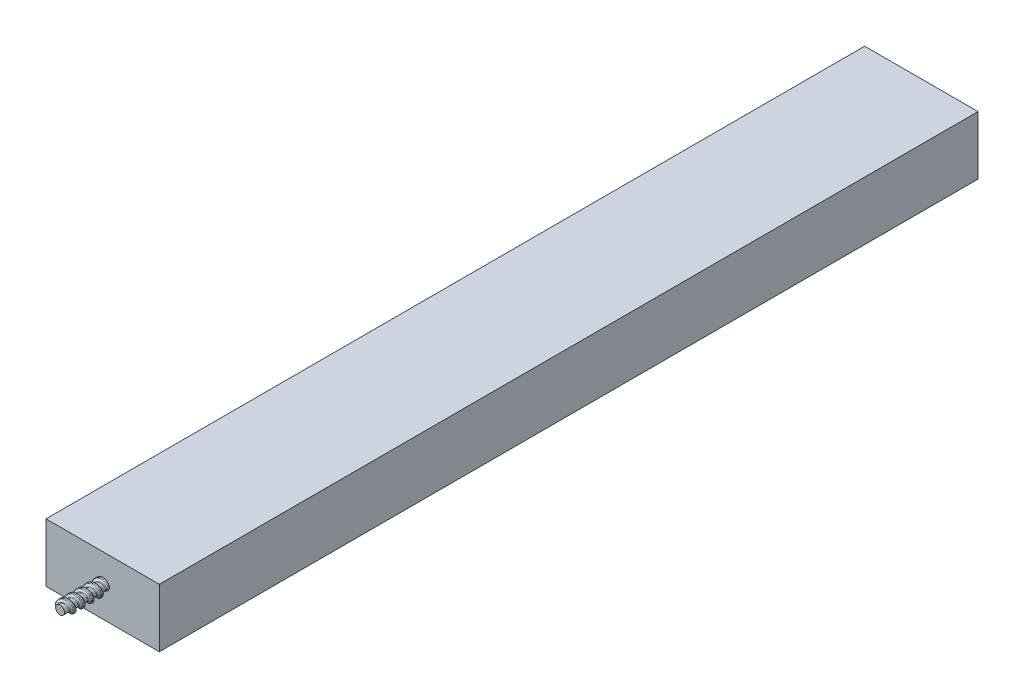
SolidWorks part; units mm, degrees
ref_plane "Front Plane" through (0, 0, 0) normal (0, 0, 1) x (1, 0, 0)
ref_plane "Top Plane" through (0, 0, 0) normal (0, 1, 0) x (1, 0, 0)
ref_plane "Right Plane" through (0, 0, 0) normal (1, 0, 0) x (0, 0, -1)
sketch "Sketch1" plane through (0, 0, 0) normal (0, 0, 1) x (1, 0, 0)
  line L1 (0, 0) -> (63.5, 0)
  line L2 (0, 0) -> (0, 32.766)
  line L3 (0, 32.766) -> (63.5, 32.766)
  line L4 (63.5, 0) -> (63.5, 32.766)
  dimension "D1" = 63.5
  dimension "D2" = 32.766
extrude "Boss-Extrude1" add sketch "Sketch1" against normal blind 482.6
sketch "Sketch2" plane through (0, 0, 0) normal (0, 0, 1) x (1, 0, 0)
  line L0 (63.5, 32.766) -> (0, 32.766) construction
  line L1 (63.5, 0) -> (63.5, 32.766) construction
  line L3 (0, 32.766) -> (63.5, 32.766)
  line L4 (0, 32.766) -> (0, 0)
  line L5 (0, 0) -> (63.5, 0)
  line L6 (63.5, 32.766) -> (63.5, 0)
  circle A0 centre (31.75, 16.383) radius 2.4574
  dimension "D1" = 4.9149
  dimension "D2" = 16.383
  dimension "D3" = 31.75
extrude "Cut-Extrude2" cut sketch "Sketch2" against normal blind 23.876
thread "Thread2" pitch 5.08 method extrude profile "Thread Profile2" start angle 0, offset 0, length 0, pitch 5.08, diameter 4.9149
ref_plane "Plane2" through (29.2926, 16.383, 0) normal (0, -1, 0) x (-1, 0, 0)
sketch "Thread Profile2" plane through (29.2926, 16.383, 0) normal (0, -1, 0) x (-1, 0, 0)
  line L0 (0, 0) -> (0, 5.08) construction
  line L1 (0, 0) -> (0, 3.6346)
  line L2 (0.508, 3.6346) -> (1.524, 3.6346) construction
  line L3 (1.524, 2.1681) -> (1.524, 1.4665)
  line L4 (1.27, 2.6081) -> (0.254, 3.1946)
  line L5 (1.27, 1.0265) -> (0.254, 0.4399)
  line L6 (0.508, 0) -> (1.524, 0) construction
  arc A0 (0.254, 3.1946) -> (0, 3.6346) centre (0.508, 3.6346) cw
  arc A1 (0.254, 0.4399) -> (0, 0) centre (0.508, 0) ccw
  arc A2 (1.524, 1.4665) -> (1.27, 1.0265) centre (1.016, 1.4665) cw
  arc A3 (1.524, 2.1681) -> (1.27, 2.6081) centre (1.016, 2.1681) ccw
  point P10 (1.524, 2.4614)
  point P17 (1.524, 1.1732)
  point P18 (0, 3.3413)
  point P19 (0, 0.2933)
  point P20 (0, 0)
  dimension "RootFillet1" = 0.508
  dimension "RootFillet2" = 0.508
  dimension "CrestFillet2" = 0.508
  dimension "CrestFillet1" = 0.508
  dimension "Pitch" = 5.08
  dimension "Angle1" = 30
  dimension "Angle2" = 30
  dimension "a" = 3.048
  dimension "b" = 1.524
  dimension "c" = 1.2882
